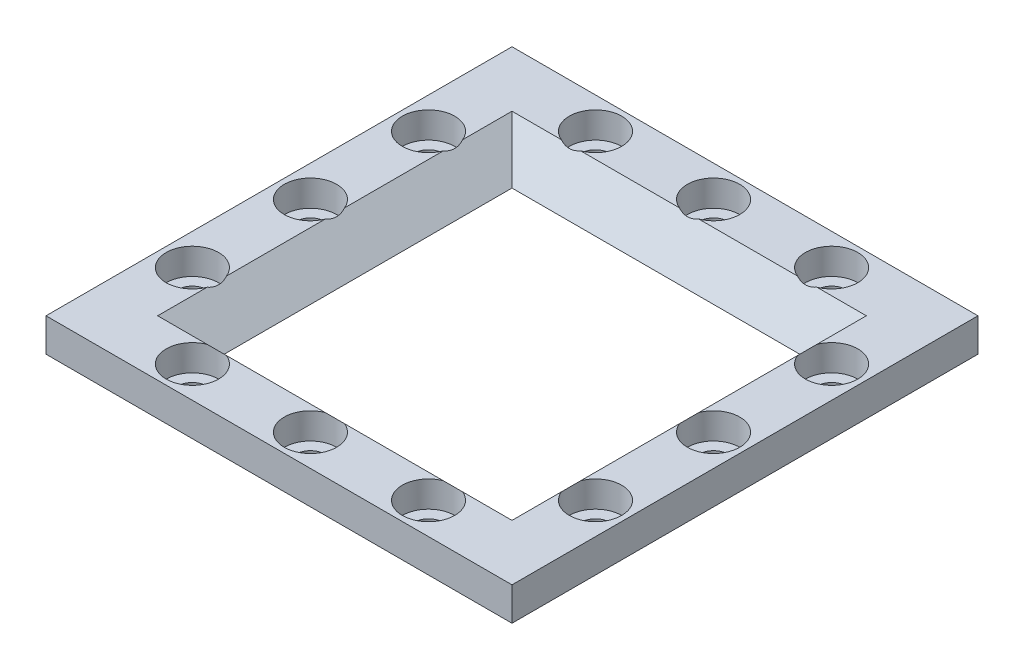
SolidWorks part; units mm, degrees
ref_plane "Front Plane" through (0, 0, 0) normal (0, 0, 1) x (1, 0, 0)
ref_plane "Top Plane" through (0, 0, 0) normal (0, 1, 0) x (1, 0, 0)
ref_plane "Right Plane" through (0, 0, 0) normal (1, 0, 0) x (0, 0, -1)
sketch "Sketch1" plane through (0, 0, 0) normal (0, 1, 0) x (1, 0, 0)
  line L0 (-38.45, 38.45) -> (-22.5235, 38.45) construction
  line L1 (-25, -25) -> (25, -25) construction
  line L2 (-25, -25) -> (-25, 25) construction
  line L3 (-25, 25) -> (25, 25) construction
  line L4 (25, -25) -> (25, 25) construction
  line L5 (-25, -25) -> (25, 25) construction
  line L6 (-25, 25) -> (25, -25) construction
  line L7 (44.45, -44.45) -> (-44.45, -44.45)
  line L8 (44.45, -44.45) -> (44.45, 44.45)
  line L9 (44.45, 44.45) -> (-44.45, 44.45)
  line L10 (-44.45, -44.45) -> (-44.45, 44.45)
  line L11 (44.45, -44.45) -> (-44.45, 44.45) construction
  line L12 (44.45, 44.45) -> (-44.45, -44.45) construction
  line L13 (32.45, -32.45) -> (-32.45, -32.45) construction
  line L14 (32.45, -32.45) -> (32.45, 32.45) construction
  line L15 (32.45, 32.45) -> (-32.45, 32.45) construction
  line L16 (-32.45, -32.45) -> (-32.45, 32.45) construction
  line L17 (32.45, -32.45) -> (-32.45, 32.45) construction
  line L18 (32.45, 32.45) -> (-32.45, -32.45) construction
  line L19 (-22.5235, 38.45) -> (0, 38.45) construction
  line L20 (0, 38.45) -> (22.5235, 38.45) construction
  line L21 (22.5235, 38.45) -> (38.45, 38.45) construction
  line L22 (38.45, 38.45) -> (38.45, 22.5235) construction
  line L23 (38.45, 22.5235) -> (38.45, 0) construction
  line L24 (38.45, 0) -> (38.45, -22.5235) construction
  line L25 (38.45, -22.5235) -> (38.45, -38.45) construction
  line L26 (38.45, -38.45) -> (22.5235, -38.45) construction
  line L27 (22.5235, -38.45) -> (0, -38.45) construction
  line L28 (0, -38.45) -> (-22.5235, -38.45) construction
  line L29 (-22.5235, -38.45) -> (-38.45, -38.45) construction
  line L30 (-38.45, -38.45) -> (-38.45, -22.5235) construction
  line L31 (-38.45, -22.5235) -> (-38.45, 0) construction
  line L32 (-38.45, 0) -> (-38.45, 22.5235) construction
  line L33 (-38.45, 22.5235) -> (-38.45, 38.45) construction
  line L34 (-38.45, 22.5235) -> (-22.5235, 38.45) construction
  line L35 (22.5235, 38.45) -> (38.45, 22.5235) construction
  line L36 (38.45, -22.5235) -> (22.5235, -38.45) construction
  line L37 (-38.45, -22.5235) -> (-22.5235, -38.45) construction
  line L38 (-32.45, 0) -> (-44.45, 0) construction
  line L40 (27.45, -27.45) -> (-27.45, -27.45)
  line L41 (27.45, -27.45) -> (27.45, 27.45)
  line L42 (27.45, 27.45) -> (-27.45, 27.45)
  line L43 (-27.45, -27.45) -> (-27.45, 27.45)
  line L44 (27.45, -27.45) -> (-27.45, 27.45) construction
  line L45 (27.45, 27.45) -> (-27.45, -27.45) construction
  circle A0 centre (-25, 25) radius 5 construction
  circle A1 centre (25, 25) radius 5 construction
  circle A2 centre (25, -25) radius 5 construction
  circle A3 centre (-25, -25) radius 5 construction
  circle A4 centre (-22.5235, 38.45) radius 4.25 construction
  circle A5 centre (0, 38.45) radius 4.25 construction
  circle A6 centre (22.5235, 38.45) radius 4.25 construction
  circle A7 centre (38.45, 22.5235) radius 4.25 construction
  circle A8 centre (38.45, 0) radius 4.25 construction
  circle A9 centre (38.45, -22.5235) radius 4.25 construction
  circle A10 centre (22.5235, -38.45) radius 4.25 construction
  circle A11 centre (0, -38.45) radius 4.25 construction
  circle A12 centre (-22.5235, -38.45) radius 4.25 construction
  circle A13 centre (-38.45, -22.5235) radius 4.25 construction
  circle A14 centre (-38.45, 0) radius 4.25 construction
  circle A15 centre (-38.45, 22.5235) radius 4.25 construction
  point P0 (0, 0)
  point P6 (0, 0)
  point P11 (0, 0)
  point P51 (0, 0)
  dimension "D4" = 10
  dimension "D5" = 8.5
  dimension "D1" = 50
  dimension "D2" = 64.9
  dimension "D3" = 12
  dimension "D6" = 5
  dimension "D7" = 88.9
extrude "Boss-Extrude1" add sketch "Sketch1" along normal blind 6.35
chamfer "Chamfer1" distance 6.35 angle 45 4 edges at (0, 6.35, 27.45) (27.45, 6.35, 0) (-27.45, 6.35, 0) (0, 6.35, -27.45)
hole_wizard "CBORE for M5 SHCS3" positions "Sketch2" profile "Sketch4" counterbore size "M5" standard "ANSI Metric" end condition through all
sketch "Sketch2" plane through (0, 6.35, 0) normal (0, 1, 0) x (1, 0, 0)
  line L0 (-32.45, 0) -> (-44.45, 0) construction
  point P0 (-22.5235, 38.45)
  point P3 (0, 38.45)
  point P6 (22.5235, 38.45)
  point P9 (38.45, 22.5235)
  point P12 (38.45, 0)
  point P15 (38.45, -22.5235)
  point P18 (22.5235, -38.45)
  point P21 (0, -38.45)
  point P24 (-22.5235, -38.45)
  point P27 (-38.45, -22.5235)
  point P30 (-38.45, 0)
  point P34 (-38.45, 22.5235)
sketch "Sketch4" plane through (-22.5235, 6.35, -38.45) normal (1, 0, 0) x (0, 0, 1)
  line L0 (0, 0) -> (0, 6.35)
  line L1 (0, 6.35) -> (2.75, 6.35)
  line L3 (2.75, 6.35) -> (2.75, 5)
  line L4 (2.75, 5) -> (5, 5)
  line L5 (5, 5) -> (5, 0)
  line L7 (5, 0) -> (0, 0)
  line L11 (0, -6.35) -> (0, 107.95) construction
  dimension "Thru Hole Dia." = 5.5
  dimension "Thru Hole Depth" = 6.35
  dimension "C'Bore Dia." = 10
  dimension "C'Bore Depth" = 5
